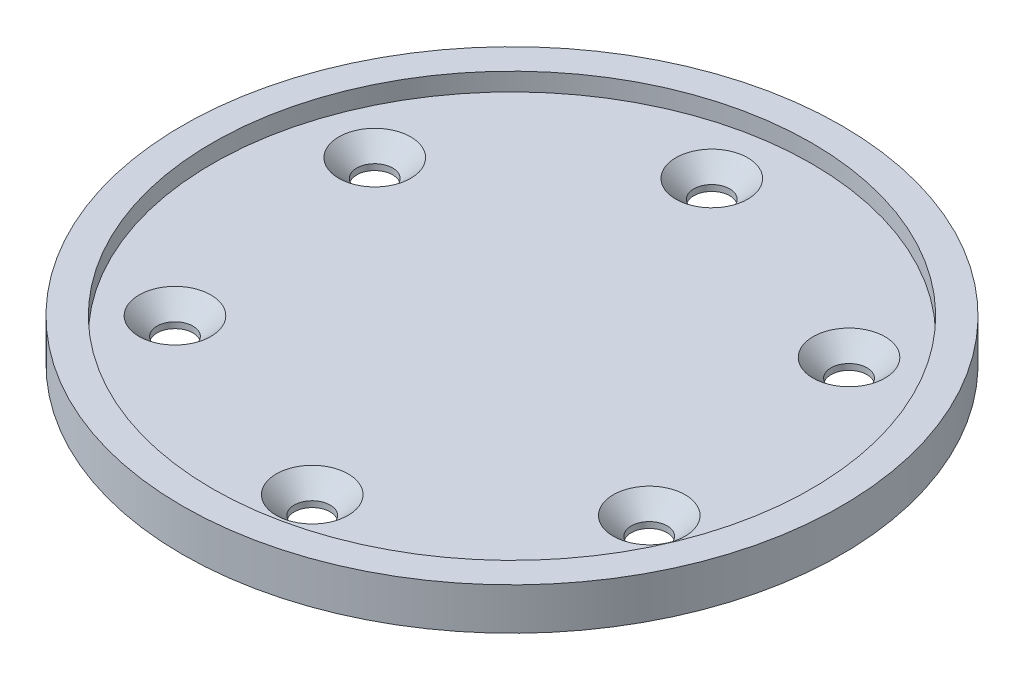
SolidWorks part; units mm, degrees
material "PBT General Purpose"
ref_plane "Front Plane" through (0, 0, 0) normal (0, 0, 1) x (1, 0, 0)
ref_plane "Top Plane" through (0, 0, 0) normal (0, 1, 0) x (1, 0, 0)
ref_plane "Right Plane" through (0, 0, 0) normal (1, 0, 0) x (0, 0, -1)
sketch "Sketch1" plane through (0, 0, 0) normal (0, 0, 1) x (1, 0, 0)
  line L0 (0, 0) -> (0, 21.4941) construction
  line L1 (50, 3.4786) -> (50, 6.4786)
  line L2 (50, 6.4786) -> (55, 6.4786)
  line L9 (50, 3.4786) -> (0, 3.4786)
  line L10 (0, -0.5214) -> (0, 3.4786)
  line L11 (0, -0.5214) -> (55, -0.5214)
  line L12 (55, -0.5214) -> (55, 6.4786)
  dimension "D2" = 50
  dimension "D5" = 5
  dimension "D3" = 4
  dimension "D7" = 3
revolve "Revolve1" add sketch "Sketch1" angle 360 about L0
sketch "Sketch2" plane through (0, 3.4786, 0) normal (0, 1, 0) x (1, 0, 0)
  circle A0 centre (-6.1774, 39.5201) radius 3
  circle A1 centre (-37.3141, 14.4103) radius 3
  circle A2 centre (-31.1367, -25.1098) radius 3
  circle A3 centre (6.1774, -39.5201) radius 3
  circle A4 centre (37.3141, -14.4103) radius 3
  circle A5 centre (31.1367, 25.1098) radius 3
  dimension "D1" = 6
extrude "Cut-Extrude1" cut sketch "Sketch2" against normal through all
chamfer "Chamfer1" distance 3 angle 45 6 edges at (31.1367, 3.4786, -22.1098) (37.3141, 3.4786, 17.4103) (-31.1367, 3.4786, 28.1098) (-37.3141, 3.4786, -11.4103) (-6.1774, 3.4786, -36.5201) (6.1774, 3.4786, 42.5201)
sketch3d "3DSketch1"
  point P0 (-57, 29.4786, 57)
